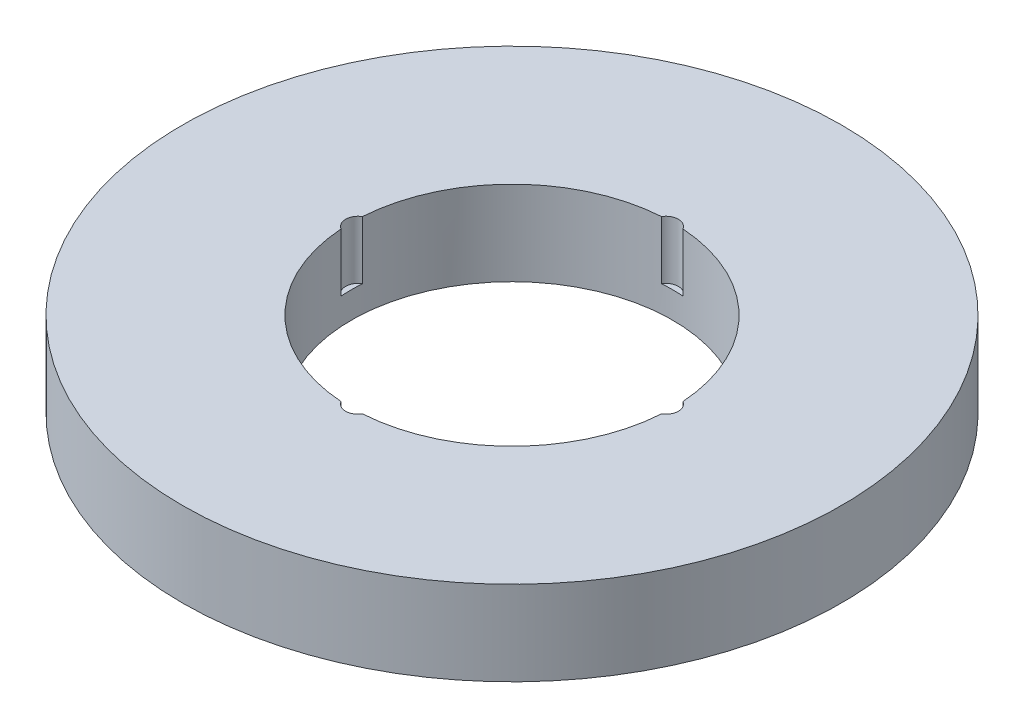
SolidWorks part; units mm, degrees
ref_plane "Front Plane" through (0, 0, 0) normal (0, 0, 1) x (1, 0, 0)
ref_plane "Top Plane" through (0, 0, 0) normal (0, 1, 0) x (1, 0, 0)
ref_plane "Right Plane" through (0, 0, 0) normal (1, 0, 0) x (0, 0, -1)
sketch "Sketch1" plane through (0, 0, 0) normal (0, 1, 0) x (1, 0, 0)
  circle A0 centre (0, 0) radius 97.5
  dimension "FLANGE_OD" = 195
extrude "Boss-Extrude1" add sketch "Sketch1" along normal blind 25
sketch "Sketch2" plane through (0, 0, 0) normal (0, 1, 0) x (1, 0, 0)
  circle A0 centre (0, 0) radius 47.5
  dimension "BORE_D" = 95
extrude "Cut-Extrude1" cut sketch "Sketch2" along normal through all
sketch "Sketch3" plane through (0, 25, 0) normal (0, 1, 0) x (1, 0, 0)
  circle A0 centre (0, 0) radius 45.5385 construction
  circle A1 centre (-45.5385, 0) radius 3.671
  dimension "BOLT_D" = 7.342
  dimension "BOLT_PCD" = 91.077
extrude "Cut-Extrude2" cut sketch "Sketch3" against normal blind 17.2044
pattern_circular "CirPattern1" count 4 over 360 about axis through (0, 0, 0) along (0, 1, 0) of "Cut-Extrude2"
